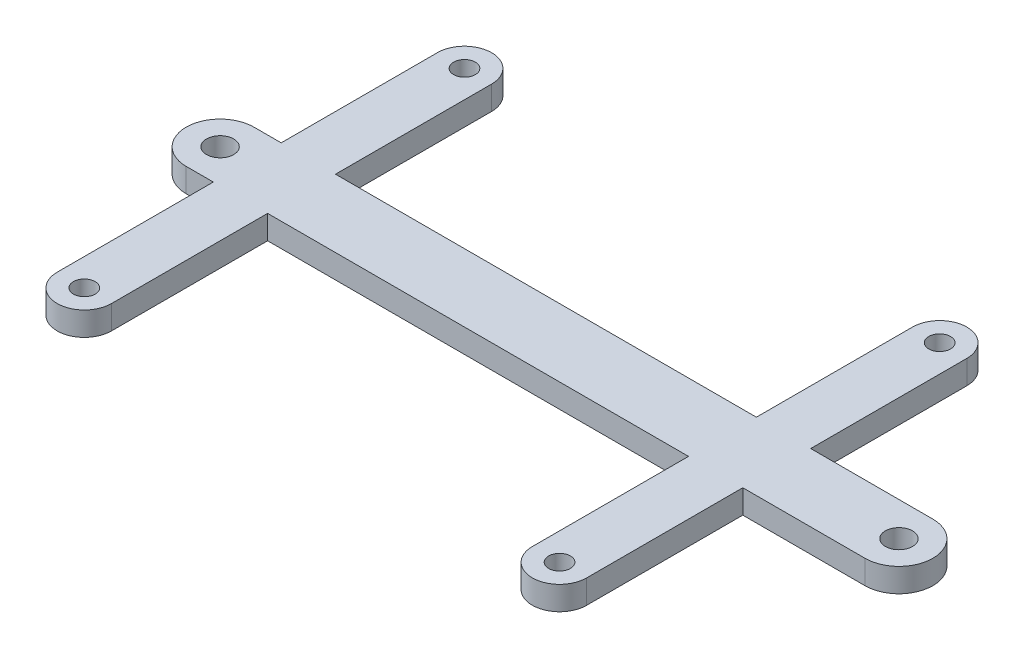
SolidWorks part; units mm, degrees
ref_plane "Front Plane" through (0, 0, 0) normal (0, 0, 1) x (1, 0, 0)
ref_plane "Top Plane" through (0, 0, 0) normal (0, 1, 0) x (1, 0, 0)
ref_plane "Right Plane" through (0, 0, 0) normal (1, 0, 0) x (0, 0, -1)
sketch "Sketch1" plane through (0, 0, 0) normal (0, 1, 0) x (1, 0, 0)
  line L0 (32, 28) -> (32, 5)
  line L4 (24, 28) -> (24, 5)
  line L5 (50, 5) -> (32, 5)
  line L16 (-50, 5) -> (-46, 5)
  line L17 (-38, 28) -> (-38, 5)
  line L18 (-46, 28) -> (-46, 5)
  line L19 (-38, 5) -> (24, 5)
  line L20 (0, 0) -> (15.6134, 0)
  line L21 (-38, -5) -> (24, -5)
  line L22 (-46, -28) -> (-46, -5)
  line L23 (-38, -28) -> (-38, -5)
  line L24 (50, -5) -> (32, -5)
  line L25 (24, -28) -> (24, -5)
  line L26 (32, -28) -> (32, -5)
  line L27 (-46, -5) -> (-50, -5)
  circle A0 centre (50, 0) radius 2
  arc A1 (50, -5) -> (50, 5) centre (50, 0) ccw
  arc A6 (-50, -5) -> (-50, 5) centre (-50, 0) cw
  circle A7 centre (-50, 0) radius 2
  circle A12 centre (28, 28) radius 1.6
  arc A13 (32, 28) -> (24, 28) centre (28, 28) ccw
  arc A14 (-38, 28) -> (-46, 28) centre (-42, 28) ccw
  circle A15 centre (-42, 28) radius 1.6
  circle A16 centre (-42, -28) radius 1.6
  arc A17 (-38, -28) -> (-46, -28) centre (-42, -28) cw
  arc A18 (32, -28) -> (24, -28) centre (28, -28) cw
  circle A19 centre (28, -28) radius 1.6
extrude "Boss-Extrude1" add sketch "Sketch1" along normal blind 3.5 contours A18 L26 L24 A1 L5 L0 A13 L4 L19 L17 A14 L18 L16 A6 L27 L22 A17 L23 L21 L25 A16 A15 A12 A0 A7 A19 region at (-3.0308, 0, 0)
